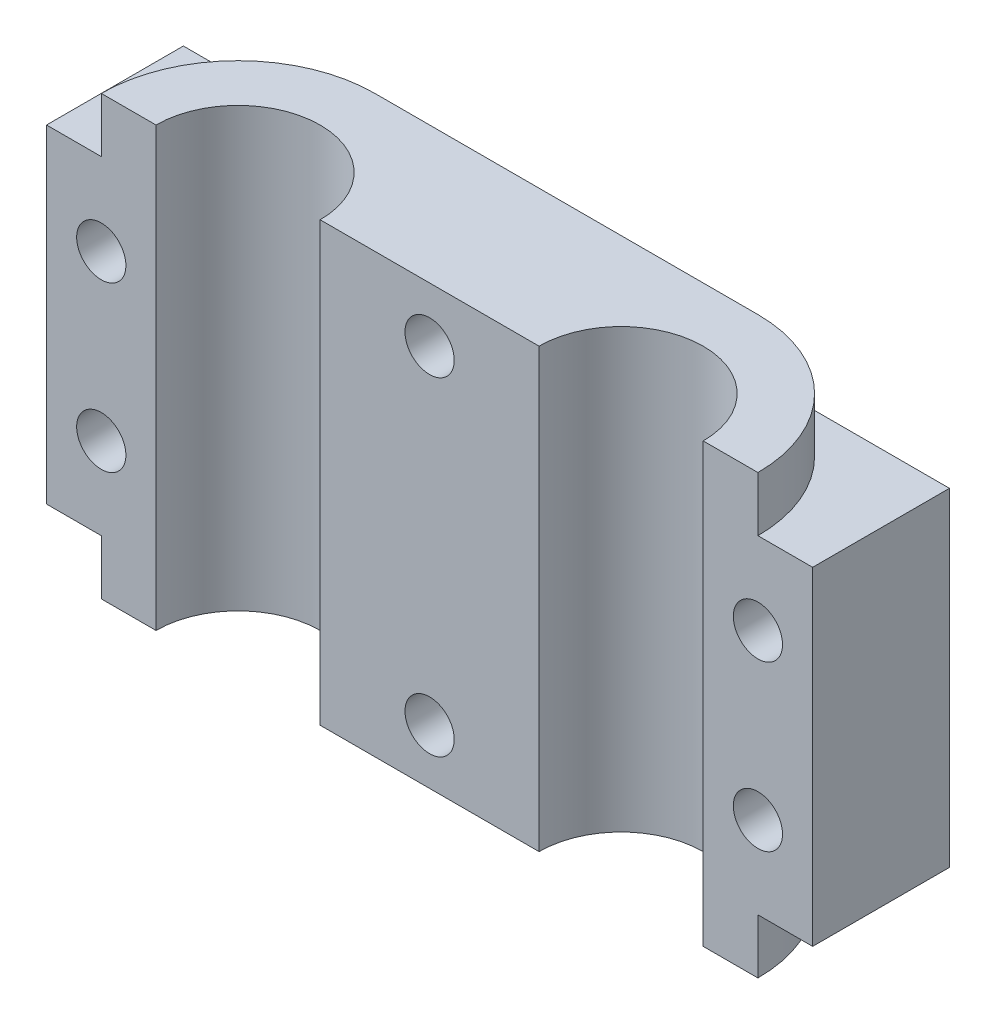
SolidWorks part; units mm, degrees
ref_plane "Front Plane" through (0, 0, 0) normal (0, 0, 1) x (1, 0, 0)
ref_plane "Top Plane" through (0, 0, 0) normal (0, 1, 0) x (1, 0, 0)
ref_plane "Right Plane" through (0, 0, 0) normal (1, 0, 0) x (0, 0, -1)
sketch "Sketch1" plane through (0, 0, 0) normal (0, 1, 0) x (1, 0, 0)
  line L0 (-35, 0) -> (35, 0)
  line L1 (-35, 0) -> (-35, -12.5)
  line L2 (-35, -12.5) -> (-25, -12.5)
  line L3 (35, -12.5) -> (35, 0)
  line L4 (0, 23.8871) -> (0, -27.5532) construction
  line L5 (-10, -12.5) -> (10, -12.5)
  line L6 (25, -12.5) -> (35, -12.5)
  arc A0 (-17.5, 0) -> (-30, -12.5) centre (-17.5, -12.5) ccw
  arc A2 (-10, -12.5) -> (-25, -12.5) centre (-17.5, -12.5) ccw
  arc A4 (10, -12.5) -> (25, -12.5) centre (17.5, -12.5) cw
  arc A5 (17.5, 0) -> (30, -12.5) centre (17.5, -12.5) cw
  point P3 (0, 0)
  dimension "D3" = 25
  dimension "D4" = 15
  dimension "D1" = 70
  dimension "D2" = 12.5
  dimension "D5" = 17.5
extrude "Boss-Extrude1" add sketch "Sketch1" along normal mid plane 40 contours L4 L0 A0 L2 A2 L5 | L0 L4 L5 A4 L6 A5 region at (-12.51, 0, 5.6375) region at (12.51, 0, 5.6375)
extrude "Boss-Extrude2" add sketch "Sketch1<3>" along normal mid plane 30 contours A0 L0 L1 L2 | L0 A5 L6 L3 region at (-30.6521, 0, 5.0426) region at (30.6521, 0, 5.0426)
sketch "Sketch1<3>" plane through (0, 0, 0) normal (0, 1, 0) x (1, 0, 0) same geometry as "Sketch1"
sketch "Sketch2" plane through (0, 0, 12.5) normal (0, 0, 1) x (1, 0, 0)
  line L0 (0, 15) -> (0, -15) construction
  line L1 (-35, 15) -> (-30, 15) construction
  circle A0 centre (0, 15) radius 2.25
  circle A1 centre (0, -15) radius 2.25
  circle A2 centre (-30, 7.5) radius 2.25
  circle A3 centre (-30, -7.5) radius 2.25
  circle A6 centre (30, -7.5) radius 2.25
  circle A7 centre (30, 7.5) radius 2.25
  dimension "D1" = 4.5
  dimension "D2" = 15
  dimension "D3" = 7.5
  dimension "D4" = 30
  dimension "D5" = 30
  dimension "D6" = 30
extrude "Cut-Extrude1" cut sketch "Sketch2" against normal blind 12.5
